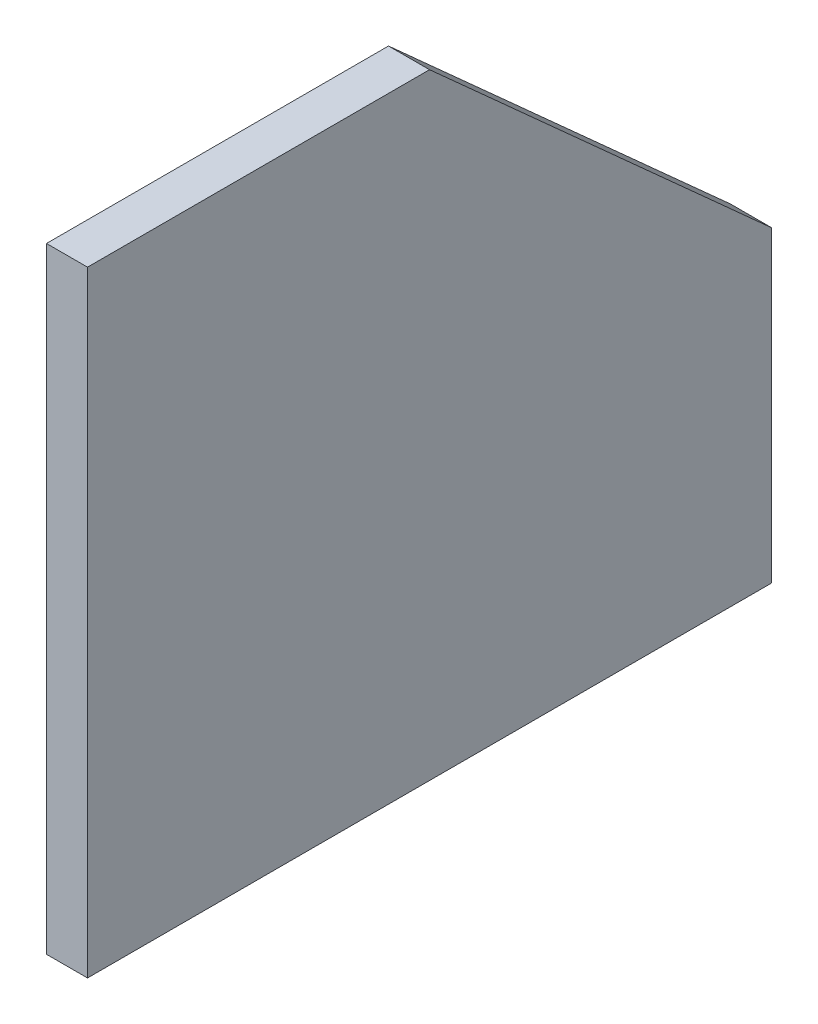
SolidWorks part; units mm, degrees
material "AISI 1020"
ref_plane "Спереди" through (0, 0, 0) normal (0, 0, 1) x (1, 0, 0)
ref_plane "Сверху" through (0, 0, 0) normal (0, 1, 0) x (1, 0, 0)
ref_plane "Справа" through (0, 0, 0) normal (1, 0, 0) x (0, 0, -1)
sketch "Эскиз1" plane through (0, 0, 0) normal (1, 0, 0) x (0, 0, -1)
  line L0 (-50, 90) -> (0, 45)
  line L1 (0, 0) -> (-100, 0)
  line L2 (0, 0) -> (0, 45)
  line L3 (-50, 90) -> (-100, 90)
  line L4 (-100, 0) -> (-100, 90)
  point P5 (-50, 0)
  point P9 (-100, 45)
  dimension "D1" = 100
  dimension "D2" = 90
base flange "Базовая кромка1" sketch "Эскиз1" thickness 6 reverse thickness direction no parameters "D1"=0.75
sketch "Сгиб-Линии1" plane through (0, 0, 0) normal (0, 1, 0) x (1, 0, 0)
sketch "Граничная рамка1" plane through (0, 0, 0) normal (0, 1, 0) x (1, 0, 0)
sheet metal parameters "Листовой металл3" thickness 6 parameters "D1"=0.75
flat pattern "Развертка3" [suppressed]
sketch "Сгиб-Линии2" plane through (0, 0, 0) normal (0, 1, 0) x (1, 0, 0)
sketch "Граничная рамка2" [suppressed] plane through (0, 0, 0) normal (0, 1, 0) x (1, 0, 0)
